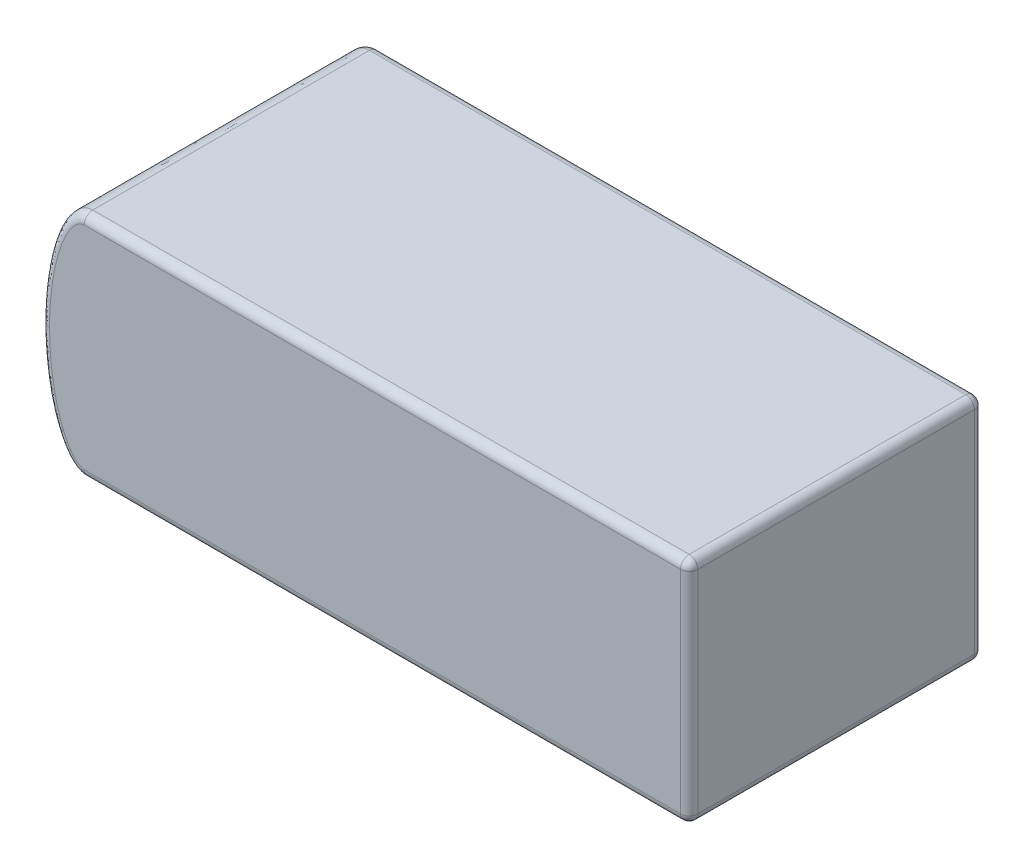
SolidWorks part; units mm, degrees
ref_plane "Front Plane" through (0, 0, 0) normal (0, 0, 1) x (1, 0, 0)
ref_plane "Top Plane" through (0, 0, 0) normal (0, 1, 0) x (1, 0, 0)
ref_plane "Right Plane" through (0, 0, 0) normal (1, 0, 0) x (0, 0, -1)
sketch "Sketch1" plane through (0, 0, 0) normal (0, 1, 0) x (1, 0, 0)
  line L1 (37.5, 17) -> (-37.5, 17)
  line L2 (37.5, 17) -> (37.5, -17)
  line L3 (37.5, -17) -> (-37.5, -17)
  line L4 (-37.5, 17) -> (-37.5, -17)
  line L5 (37.5, 17) -> (-37.5, -17) construction
  line L6 (37.5, -17) -> (-37.5, 17) construction
  point P0 (0, 0)
  dimension "D1" = 75
  dimension "D2" = 34
extrude "Boss-Extrude1" add sketch "Sketch1" along normal blind 26.5
ref_plane "Plane1" through (-37.5, 0, 0) normal (-1, 0, 0) x (0, 0, 1)
fillet "Fillet3" radius 13.25 2 edges at (-37.5, 0, 0) (-37.5, 26.5, 0) second distance 5 first distance on face at (-37.5, 13.25, 0)
fillet "Fillet4" radius 1 12 edges at (37.5, 13.25, 17) (37.5, 13.25, -17) (37.5, 0, 0) (37.5, 26.5, 0)
